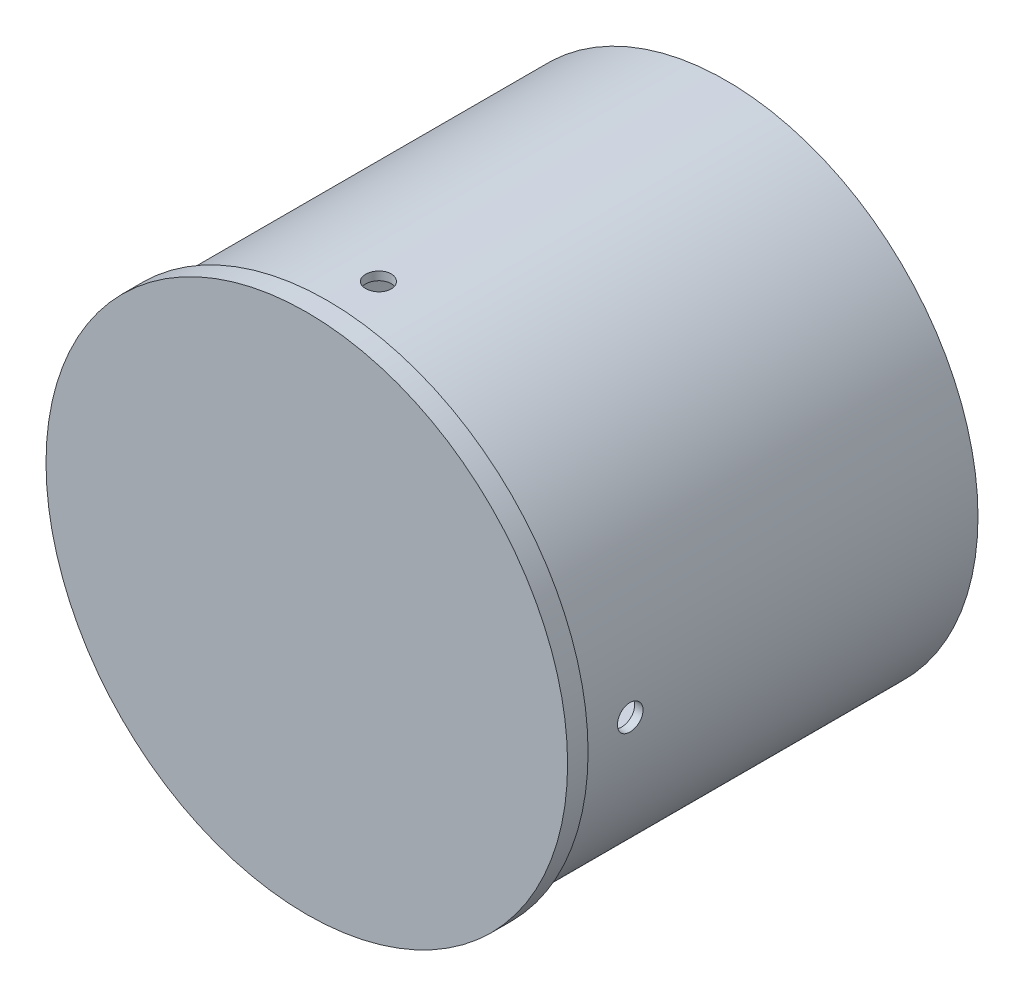
SolidWorks part; units mm, degrees
ref_plane "Front Plane" through (0, 0, 0) normal (0, 0, 1) x (1, 0, 0)
ref_plane "Top Plane" through (0, 0, 0) normal (0, 1, 0) x (1, 0, 0)
ref_plane "Right Plane" through (0, 0, 0) normal (1, 0, 0) x (0, 0, -1)
sketch "Sketch1" plane through (0, 0, 0) normal (0, 0, 1) x (1, 0, 0)
  circle A0 centre (0, 0) radius 47.6
  circle A1 centre (0, 0) radius 49.25
  dimension "D1" = 95.2
  dimension "D2" = 98.5
extrude "Boss-Extrude1" add sketch "Sketch1" along normal mid plane 280
ref_plane "Plane1" through (50, 0, 0) normal (1, 0, 0) x (0, 0, -1)
sketch "Sketch2" plane through (50, 0, 0) normal (1, 0, 0) x (0, 0, -1)
  line L0 (-140, 49.25) -> (-140, -49.25) construction
  circle A0 centre (-130, 0) radius 2.5
  dimension "D2" = 5
  dimension "D1" = 10
extrude "Cut-Extrude1" cut sketch "Sketch2" against normal blind 20
pattern_circular "CirPattern1" count 4 over 360 about axis through (0, 0, 140) along (0, 0, 1) of "Cut-Extrude1"
ref_plane "Plane2" through (0, 0, 130) normal (0, 0, 1) x (1, 0, 0)
mirror "Mirror1" about plane through (0, 0, 0) normal (0, 0, 1) of "CirPattern1", "Cut-Extrude1"
sketch "Sketch3" plane through (0, 0, 0) normal (1, 0, 0) x (0, 0, -1)
  line L0 (-140, 49.25) -> (-140, -49.25) construction
  line L3 (-140, 0) -> (140, 0) construction
  circle A0 centre (-110, 30) radius 1.5
  circle A1 centre (-100, 30) radius 1.5
  circle A2 centre (-90, 30) radius 1.5
  circle A3 centre (-80, 30) radius 1.5
  circle A4 centre (-70, 30) radius 1.5
  circle A5 centre (-60, 30) radius 1.5
  circle A6 centre (-50, 30) radius 1.5
  circle A7 centre (-40, 30) radius 1.5
  circle A8 centre (-30, 30) radius 1.5
  circle A9 centre (-20, 30) radius 1.5
  circle A10 centre (-10, 30) radius 1.5
  circle A11 centre (0, 30) radius 1.5
  circle A12 centre (10, 30) radius 1.5
  circle A13 centre (20, 30) radius 1.5
  circle A14 centre (30, 30) radius 1.5
  circle A15 centre (40, 30) radius 1.5
  circle A16 centre (50, 30) radius 1.5
  circle A17 centre (60, 30) radius 1.5
  circle A18 centre (70, 30) radius 1.5
  circle A19 centre (80, 30) radius 1.5
  dimension "D1" = 3
  dimension "D2" = 30
  dimension "D3" = 30
  dimension "D4" = 20
extrude "Cut-Extrude2" cut sketch "Sketch3" against normal through all
pattern_circular "CirPattern2" count 12 every 15 about axis through (0, 0, 140) along (0, 0, 1) of "Cut-Extrude2"
sketch "Sketch4" plane through (0, 0, 140) normal (0, 0, 1) x (1, 0, 0)
  circle A0 centre (0, 0) radius 51
  dimension "102" = 102
extrude "Boss-Extrude2" add sketch "Sketch4" along normal blind 4
ref_plane "Plane3" through (0, 0, 62) normal (0, 0, 1) x (1, 0, 0)
sketch "Sketch7" plane through (0, 0, 62) normal (0, 0, 1) x (1, 0, 0)
  circle A0 centre (0, 0) radius 55
  dimension "D1" = 110
extrude "Cut-Extrude3" cut sketch "Sketch7" against normal up to surface (202 mm away)
